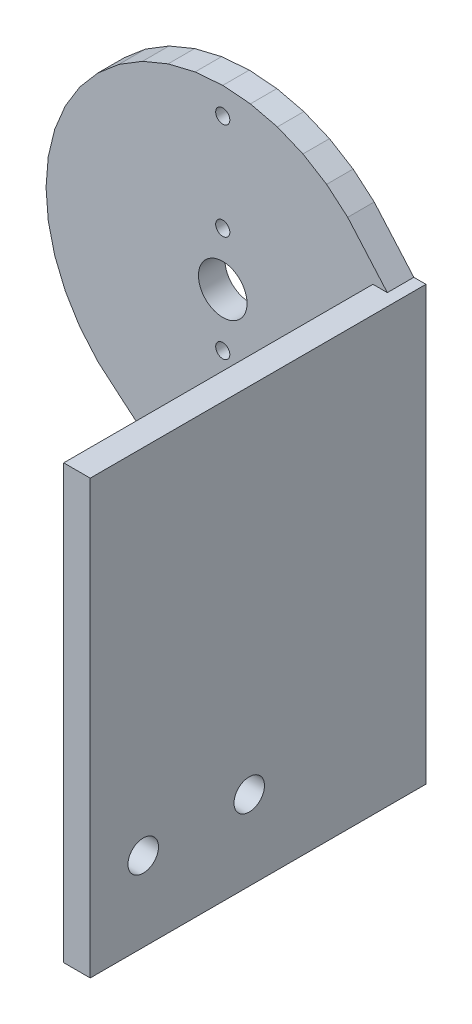
SolidWorks part; units mm, degrees
ref_plane "Front Plane" through (0, 0, 0) normal (0, 0, 1) x (1, 0, 0)
ref_plane "Top Plane" through (0, 0, 0) normal (0, 1, 0) x (1, 0, 0)
ref_plane "Right Plane" through (0, 0, 0) normal (1, 0, 0) x (0, 0, -1)
sketch "Sketch1" plane through (0, 0, 0) normal (0, 0, 1) x (1, 0, 0)
  line L0 (-20, 0) -> (-19.7538, -3.1287)
  line L1 (-19.7538, -3.1287) -> (-19.0211, -6.1803)
  line L2 (-19.0211, -6.1803) -> (-17.8201, -9.0798)
  line L3 (-17.8201, -9.0798) -> (-16.1803, -11.7557)
  line L4 (-16.1803, -11.7557) -> (-14.1421, -14.1421)
  line L5 (-14.1421, -14.1421) -> (-11.7557, -16.1803)
  line L6 (-11.7557, -16.1803) -> (16.0305, -39.5225)
  line L7 (16.0305, -39.5225) -> (16.365, -39.7275)
  line L8 (16.365, -39.7275) -> (16.7275, -39.8776)
  line L9 (16.7275, -39.8776) -> (17.1089, -39.9692)
  line L10 (17.1089, -39.9692) -> (17.5, -40)
  line L11 (17.5, -40) -> (17.8911, -39.9692)
  line L12 (17.8911, -39.9692) -> (18.2725, -39.8776)
  line L13 (18.2725, -39.8776) -> (18.635, -39.7275)
  line L14 (18.635, -39.7275) -> (18.9695, -39.5225)
  line L15 (18.9695, -39.5225) -> (19.2678, -39.2678)
  line L16 (19.2678, -39.2678) -> (19.5225, -38.9695)
  line L17 (19.5225, -38.9695) -> (19.7275, -38.635)
  line L18 (19.7275, -38.635) -> (19.8776, -38.2725)
  line L19 (19.8776, -38.2725) -> (19.9692, -37.8911)
  line L20 (19.9692, -37.8911) -> (20, -37.5)
  line L21 (20, -37.5) -> (20, 6.5)
  line L22 (20, 6.5) -> (19.9692, 6.8911)
  line L23 (19.9692, 6.8911) -> (19.8776, 7.2725)
  line L24 (19.8776, 7.2725) -> (19.7275, 7.635)
  line L25 (19.7275, 7.635) -> (19.5225, 7.9695)
  line L26 (19.5225, 7.9695) -> (19.2678, 8.2678)
  line L27 (19.2678, 8.2678) -> (14.1421, 14.1421)
  line L28 (14.1421, 14.1421) -> (11.7557, 16.1803)
  line L29 (11.7557, 16.1803) -> (9.0798, 17.8201)
  line L30 (9.0798, 17.8201) -> (6.1803, 19.0211)
  line L31 (6.1803, 19.0211) -> (3.1287, 19.7538)
  line L32 (3.1287, 19.7538) -> (0, 20)
  line L33 (0, 20) -> (-3.1287, 19.7538)
  line L34 (-3.1287, 19.7538) -> (-6.1803, 19.0211)
  line L35 (-6.1803, 19.0211) -> (-9.0798, 17.8201)
  line L36 (-9.0798, 17.8201) -> (-11.7557, 16.1803)
  line L37 (-11.7557, 16.1803) -> (-14.1421, 14.1421)
  line L38 (-14.1421, 14.1421) -> (-16.1803, 11.7557)
  line L39 (-16.1803, 11.7557) -> (-17.8201, 9.0798)
  line L40 (-17.8201, 9.0798) -> (-19.0211, 6.1803)
  line L41 (-19.0211, 6.1803) -> (-19.7538, 3.1287)
  line L42 (-19.7538, 3.1287) -> (-20, 0)
extrude "Boss-Extrude1" add sketch "Sketch1" along normal blind 3 from offset 26 offset against normal yes
sketch "Sketch2" plane through (0, 0, 0) normal (0, 0, 1) x (1, 0, 0)
  line L0 (17, -40) -> (20, -40)
  line L1 (20, -40) -> (20, 9)
  line L2 (20, 9) -> (17, 9)
  line L3 (17, 9) -> (17, -40)
extrude "Boss-Extrude2" add sketch "Sketch2" along normal blind 38 from offset 26 offset against normal yes
sketch "Sketch3" plane through (0, 0, 0) normal (0, 0, 1) x (1, 0, 0)
  circle A0 centre (0, 0) radius 2.75
  circle A1 centre (0, 6) radius 0.8
  circle A2 centre (0, -6) radius 0.8
  circle A3 centre (0, 17) radius 0.8
  circle A4 centre (0, -17) radius 0.8
extrude "Cut-Extrude1" cut sketch "Sketch3" against normal through all and the other way through all
sketch "Sketch4" plane through (0, 0, 0) normal (1, 0, 0) x (0, 0, -1)
  circle A0 centre (-6, -31) radius 1.725
  circle A1 centre (6, -31) radius 1.725
extrude "Cut-Extrude2" cut sketch "Sketch4" against normal through all and the other way through all
